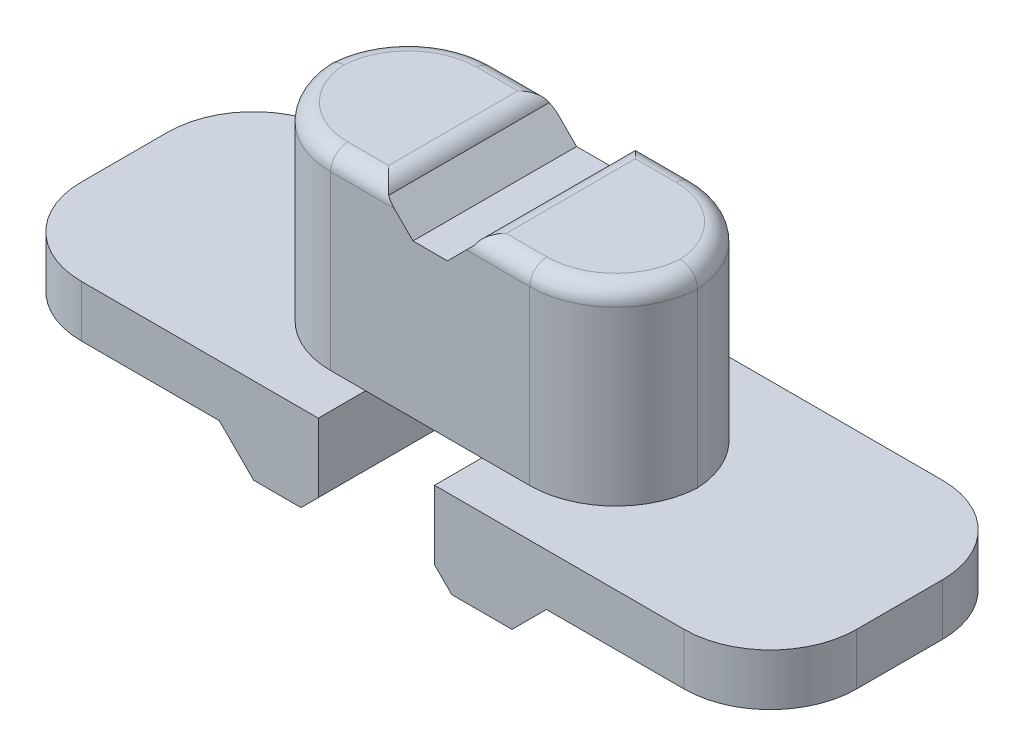
SolidWorks part; units mm, degrees
ref_plane "前视基准面" through (0, 0, 0) normal (0, 0, 1) x (1, 0, 0)
ref_plane "上视基准面" through (0, 0, 0) normal (0, 1, 0) x (1, 0, 0)
ref_plane "右视基准面" through (0, 0, 0) normal (1, 0, 0) x (0, 0, -1)
sketch "草图1" plane through (0, 0, 0) normal (0, 1, 0) x (1, 0, 0)
  line L1 (-4.0252, 1.9436) -> (4.9748, 1.9436)
  line L2 (-4.0252, 1.9436) -> (-4.0252, -1.0564)
  line L3 (-4.0252, -1.0564) -> (4.9748, -1.0564)
  line L4 (4.9748, 1.9436) -> (4.9748, -1.0564)
  line L5 (-4.0252, 1.9436) -> (4.9748, -1.0564) construction
  line L6 (-4.0252, -1.0564) -> (4.9748, 1.9436) construction
  point P0 (0.4748, 0.4436)
  dimension "D1" = 9
  dimension "D2" = 3
extrude "凸台-拉伸1" add sketch "草图1" along normal blind 0.6
sketch "草图2" plane through (0, 0.6, 0) normal (0, 1, 0) x (1, 0, 0)
  line L1 (-1.681, 1.3936) -> (2.6305, 1.3936)
  line L2 (-1.681, 1.3936) -> (-1.681, -0.5064)
  line L3 (-1.681, -0.5064) -> (2.6305, -0.5064)
  line L4 (2.6305, 1.3936) -> (2.6305, -0.5064)
  line L5 (-1.681, 1.3936) -> (2.6305, -0.5064) construction
  line L6 (-1.681, -0.5064) -> (2.6305, 1.3936) construction
  line L7 (4.9748, -1.0564) -> (4.9748, 1.9436) construction
  line L8 (4.9748, 1.9436) -> (-4.0252, 1.9436) construction
  point P0 (0.4748, 0.4436)
  point P12 (4.9748, 0.4436)
  point P17 (0.4748, 1.9436)
  dimension "D1" = 1.9
extrude "凸台-拉伸2" add sketch "草图2" along normal blind 2.2
fillet "圆角1" radius 1 8 edges at (-4.0252, 0.3, 1.0564) (-1.681, 1.7, 0.5064) (4.9748, 0.3, 1.0564) (2.6305, 1.7, 0.5064) (-1.681, 1.7, -1.3936) (2.6305, 1.7, -1.3936) (4.9748, 0.3, -1.9436) (-4.0252, 0.3, -1.9436)
sketch "草图3" plane through (0, 0, 0) normal (0, -1, 0) x (1, 0, 0)
  line L0 (3.9748, -1.9436) -> (-3.0252, -1.9436) construction
  line L1 (1.9748, -1.9436) -> (-1.0252, -1.9436)
  line L2 (1.9748, -1.9436) -> (1.9748, 1.0564)
  line L3 (1.9748, 1.0564) -> (-1.0252, 1.0564)
  line L4 (-1.0252, -1.9436) -> (-1.0252, 1.0564)
  line L5 (-3.0252, 1.0564) -> (3.9748, 1.0564) construction
  line L6 (4.9748, 0.0564) -> (4.9748, -0.9436) construction
  dimension "D1" = 3
  dimension "D2" = 3
extrude "凸台-拉伸3" add sketch "草图3" along normal blind 0.4
chamfer "倒角1" distance 0.4 angle 45 2 edges at (1.9748, 0, -0.4436) (-1.0252, 0, -0.4436)
sketch "草图5" plane through (0, 0, -1.9436) normal (0, 0, -1) x (-1, 0, 0)
  line L1 (0.2752, -0.4) -> (-1.0748, -0.4)
  line L2 (0.2752, -0.4) -> (0.2752, 0.6)
  line L3 (0.2752, 0.6) -> (-1.0748, 0.6)
  line L4 (-1.0748, -0.4) -> (-1.0748, 0.6)
  line L5 (-4.9748, 0) -> (-4.9748, 0.6) construction
  line L6 (1.0252, -0.4) -> (-1.9748, -0.4) construction
  dimension "D1" = 1.35
  dimension "D2" = 3.9
  dimension "D3" = 1
extrude "切除-拉伸1" cut sketch "草图5" against normal up to next
chamfer "倒角2" distance 0.2 angle 45 2 edges at (1.0748, -0.4, -0.4436) (-0.2752, -0.4, -0.4436)
sketch "草图7" plane through (0, 0, 0.5064) normal (0, 0, 1) x (1, 0, 0)
  line L1 (0.9748, 2.3818) -> (-0.0252, 2.3818)
  line L2 (0.9748, 2.3818) -> (0.9748, 2.8182)
  line L3 (0.9748, 2.8182) -> (-0.0252, 2.8182)
  line L4 (-0.0252, 2.3818) -> (-0.0252, 2.8182)
  line L5 (0.9748, 2.3818) -> (-0.0252, 2.8182) construction
  line L6 (0.9748, 2.8182) -> (-0.0252, 2.3818) construction
  point P0 (0.4748, 2.6)
  dimension "D1" = 1
extrude "切除-拉伸2" cut sketch "草图7" against normal up to next and the other way through all
chamfer "倒角3" distance 0.3 angle 45 2 edges at (0.9748, 2.3818, -0.4436) (-0.0252, 2.3818, -0.4436)
fillet "圆角2" radius 0.2 10 edges at (-1.3702, 2.8, 0.2309) (-1.3702, 2.8, -1.1182) (-0.3531, 2.8, -1.3936) (-0.3531, 2.8, 0.5064) (2.3197, 2.8, -1.1182) (2.3197, 2.8, 0.2309) (1.3026, 2.8, 0.5064) (1.3026, 2.8, -1.3936) (-0.0252, 2.8, -0.4436) (0.9748, 2.8, -0.4436)
